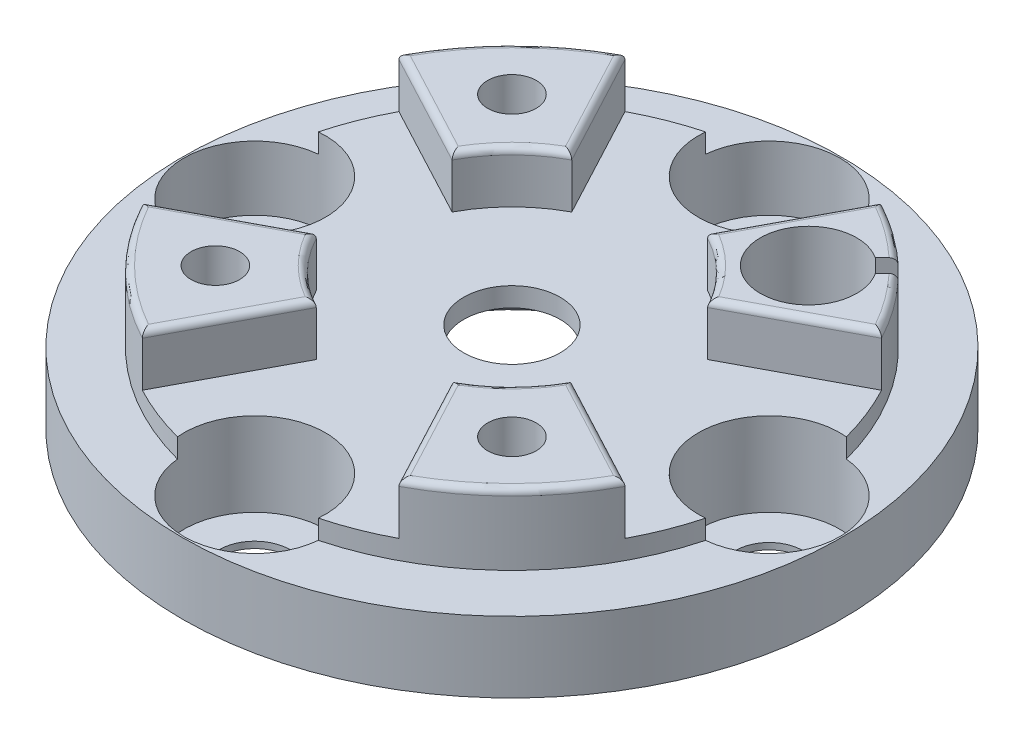
SolidWorks part; units mm, degrees
ref_plane "Front Plane" through (0, 0, 0) normal (0, 0, 1) x (1, 0, 0)
ref_plane "Top Plane" through (0, 0, 0) normal (0, 1, 0) x (1, 0, 0)
ref_plane "Right Plane" through (0, 0, 0) normal (1, 0, 0) x (0, 0, -1)
sketch "Sketch2" plane through (0, 0, 0) normal (0, 1, 0) x (1, 0, 0)
  circle A0 centre (0, 0) radius 10.25
  circle A1 centre (8, 0) radius 1.05
  circle A2 centre (0, 8) radius 1.1
  circle A3 centre (-8, 0) radius 1.05
  circle A4 centre (0, -8) radius 1.1
  dimension "D1" = 20.5
  dimension "D6" = 2.1
  dimension "D7" = 2.1
  dimension "D8" = 2.2
  dimension "D9" = 2.2
  dimension "D2" = 8
  dimension "D3" = 16
  dimension "D4" = 8
  dimension "D5" = 16
extrude "Boss-Extrude1" add sketch "Sketch2" along normal blind 2.2
sketch "Sketch3" plane through (0, 2.2, 0) normal (0, 1, 0) x (1, 0, 0)
  circle A0 centre (0, 8) radius 2.2
  circle A1 centre (-8, 0) radius 2.2
  circle A2 centre (0, -8) radius 2.2
  circle A3 centre (8, 0) radius 2.2
extrude "Cut-Extrude1" cut sketch "Sketch3" against normal blind 2
sketch "Sketch4" plane through (0, 2.2, 0) normal (0, 1, 0) x (1, 0, 0)
  circle A0 centre (0, 0) radius 4.125
  dimension "D1" = 8.25
extrude "Cut-Extrude2" cut sketch "Sketch4" against normal through all
sketch "Sketch7" plane through (0, 2.2, 0) normal (0, 1, 0) x (1, 0, 0)
  arc A0 (2.1897, -8.2131) -> (8.2131, -2.1897) centre (0, 0) ccw
  arc A1 (-8.2131, -2.1897) -> (-8.2131, 2.1897) centre (-8, 0) ccw
  arc A3 (-2.1897, 8.2131) -> (2.1897, 8.2131) centre (0, 8) ccw
  arc A4 (2.1897, -8.2131) -> (-2.1897, -8.2131) centre (0, -8) ccw
  arc A5 (-8.2131, -2.1897) -> (-2.1897, -8.2131) centre (0, 0) ccw
  arc A6 (-2.1897, 8.2131) -> (-8.2131, 2.1897) centre (0, 0) ccw
  arc A7 (8.2131, 2.1897) -> (2.1897, 8.2131) centre (0, 0) ccw
  arc A8 (8.2131, 2.1897) -> (8.2131, -2.1897) centre (8, 0) ccw
  dimension "D1" = 17
extrude "Boss-Extrude3" add sketch "Sketch7" along normal blind 0.6
sketch "Sketch8" plane through (0, 2.8, 0) normal (0, 1, 0) x (1, 0, 0)
  circle A0 centre (0, 0) radius 1.5
  dimension "D1" = 3
extrude "Cut-Extrude7" cut sketch "Sketch8" against normal blind 0.6
chamfer "Chamfer2" distance 0.5 angle 40 1 edges at (0, 0, 4.125) first distance on face at (0, 0, 4.125)
sketch "Sketch10" plane through (0, 0, 0) normal (0, -1, 0) x (-1, 0, 0)
  line L0 (0, 8.5) -> (0, 0) construction
  line L1 (0, 0) -> (-8.5, 0) construction
  line L2 (-6.0104, 6.0104) -> (-3.2135, 3.2135) construction
  arc A0 (0, 8.5) -> (-8.5, 0) centre (0, 0) ccw construction
  circle A1 centre (0, 0) radius 4.5445 construction
  circle A2 centre (-4.6119, 4.6119) radius 0.76
  dimension "D1" = 1.52
extrude "Cut-Extrude8" cut sketch "Sketch10" against normal through all
sketch "Sketch11" plane through (0, 2.8, 0) normal (0, 1, 0) x (1, 0, 0)
  circle A0 centre (4.6119, 4.6119) radius 1.5
extrude "Cut-Extrude9" cut sketch "Sketch11" against normal blind 1
sketch "Sketch12" plane through (0, 2.8, 0) normal (0, 1, 0) x (1, 0, 0)
  line L0 (0, 0) -> (4.6119, 4.6119) construction
  line L1 (4.6119, 4.6119) -> (7.2478, 7.2478)
  circle A0 centre (0, 0) radius 10.25 construction
extrude "Cut-Extrude-Thin1" cut sketch "Sketch12" against normal blind 0.6 and the other way through all thin thin type mid plane wall 0.6
sketch "Sketch13" plane through (0, 2.8, 0) normal (0, 1, 0) x (1, 0, 0)
  line L0 (4.6119, 4.6119) -> (0, 0) construction
  line L1 (0, 0) -> (-4.6119, -4.6119) construction
  circle A0 centre (-4.6119, -4.6119) radius 0.755
  dimension "D1" = 1.51
extrude "Cut-Extrude10" cut sketch "Sketch13" against normal through all both and the other way through all
sketch "Sketch14" plane through (0, 2.8, 0) normal (0, 1, 0) x (1, 0, 0)
  line L0 (0, 0) -> (-4.6119, -4.6119) construction
  line L1 (-4.6119, -4.6119) -> (-4.6119, 4.6119) construction
  line L2 (0, 0) -> (4.6119, 4.6119) construction
  line L3 (4.6119, 4.6119) -> (4.6119, -4.6119) construction
  line L4 (4.6119, 4.6119) -> (-4.6119, 4.6119) construction
  line L5 (-4.6119, -4.6119) -> (4.6119, -4.6119) construction
  circle A0 centre (4.6119, -4.6119) radius 0.755
  circle A1 centre (-4.6119, 4.6119) radius 0.755
  circle A2 centre (-4.6119, -4.6119) radius 0.755 construction
extrude "Cut-Extrude11" cut sketch "Sketch14" against normal blind 10
sketch "Sketch16" plane through (0, 2.8, 0) normal (0, 1, 0) x (1, 0, 0)
  line L0 (0, 0) -> (6.0104, -6.0104) construction
  line L1 (0, 0) -> (-6.0104, -6.0104) construction
  line L2 (0, 0) -> (-6.0104, 6.0104) construction
  line L3 (0, 0) -> (6.0104, 6.0104) construction
  line L4 (0, 0) -> (-7.5051, -3.9905) construction
  line L5 (0, 0) -> (-3.9905, -7.5051) construction
  line L6 (0, 0) -> (7.5051, 3.9905) construction
  line L7 (0, 0) -> (3.9905, 7.5051) construction
  line L8 (0, 0) -> (-7.5051, 3.9905) construction
  line L9 (0, 0) -> (-3.9905, 7.5051) construction
  line L10 (0, 0) -> (7.5051, -3.9905) construction
  line L11 (0, 0) -> (3.9905, -7.5051) construction
  line L12 (-2.7076, -5.0922) -> (-3.9905, -7.5051)
  line L13 (-5.0922, -2.7076) -> (-7.5051, -3.9905)
  line L14 (-5.0922, 2.7076) -> (-7.5051, 3.9905)
  line L15 (-2.7076, 5.0922) -> (-3.9905, 7.5051)
  line L16 (2.7076, 5.0922) -> (3.9905, 7.5051)
  line L17 (5.0922, 2.7076) -> (7.5051, 3.9905)
  line L18 (5.0922, -2.7076) -> (7.5051, -3.9905)
  line L19 (2.7076, -5.0922) -> (3.9905, -7.5051)
  line L20 (5.7945, 6.2188) -> (5.439, 5.8633)
  line L21 (6.2188, 5.7945) -> (5.8633, 5.439)
  line L22 (-2.7076, -5.0922) -> (-2.1126, -3.9733)
  line L23 (-5.0922, -2.7076) -> (-3.9733, -2.1126)
  line L24 (-5.0922, 2.7076) -> (-3.9733, 2.1126)
  line L25 (-2.7076, 5.0922) -> (-2.1126, 3.9733)
  line L26 (2.7076, 5.0922) -> (2.1126, 3.9733)
  line L27 (5.0922, 2.7076) -> (3.9733, 2.1126)
  line L28 (5.0922, -2.7076) -> (3.9733, -2.1126)
  line L29 (2.7076, -5.0922) -> (2.1126, -3.9733)
  arc A0 (2.1897, -8.2131) -> (8.2131, -2.1897) centre (0, 0) ccw construction
  arc A1 (-8.2131, -2.1897) -> (-2.1897, -8.2131) centre (0, 0) ccw construction
  arc A2 (-2.1897, 8.2131) -> (-8.2131, 2.1897) centre (0, 0) ccw construction
  arc A3 (-8.2131, -2.1897) -> (-2.1897, -8.2131) centre (0, 0) ccw construction
  arc A4 (8.2131, 2.1897) -> (6.2188, 5.7945) centre (0, 0) ccw construction
  arc A5 (5.7945, 6.2188) -> (2.1897, 8.2131) centre (0, 0) ccw construction
  arc A6 (-2.1897, 8.2131) -> (-8.2131, 2.1897) centre (0, 0) ccw construction
  arc A7 (2.1897, -8.2131) -> (8.2131, -2.1897) centre (0, 0) ccw construction
  arc A9 (3.9905, -7.5051) -> (7.5051, -3.9905) centre (0, 0) ccw
  arc A11 (-7.5051, -3.9905) -> (-3.9905, -7.5051) centre (0, 0) ccw
  arc A12 (-3.9905, 7.5051) -> (-7.5051, 3.9905) centre (0, 0) ccw
  arc A14 (7.5051, 3.9905) -> (6.2188, 5.7945) centre (0, 0) ccw
  circle A16 centre (-4.6119, -4.6119) radius 0.755
  circle A17 centre (-4.6119, 4.6119) radius 0.755
  circle A19 centre (4.6119, -4.6119) radius 0.755
  arc A22 (5.7945, 6.2188) -> (3.9905, 7.5051) centre (0, 0) ccw
  arc A23 (3.9733, 2.1126) -> (2.1126, 3.9733) centre (0, 0) ccw
  circle A24 centre (4.6119, 4.6119) radius 1.5
  arc A25 (-2.1126, 3.9733) -> (-3.9733, 2.1126) centre (0, 0) ccw
  arc A26 (-3.9733, -2.1126) -> (-2.1126, -3.9733) centre (0, 0) ccw
  arc A27 (2.1126, -3.9733) -> (3.9733, -2.1126) centre (0, 0) ccw
  circle M12 centre (4.6119, -4.6119) radius 0.755
  circle M13 centre (-4.6119, 4.6119) radius 0.755
  circle M14 centre (-4.6119, -4.6119) radius 0.755
  arc M16 (8.2131, 2.1897) -> (6.2188, 5.7945) centre (0, 0) ccw
  line M17 (6.2188, 5.7945) -> (5.8633, 5.439)
  arc M18 (5.8633, 5.439) -> (5.439, 5.8633) centre (4.6119, 4.6119) cw
  line M19 (5.439, 5.8633) -> (5.7945, 6.2188)
  arc M20 (5.7945, 6.2188) -> (2.1897, 8.2131) centre (0, 0) ccw
  arc M22 (-2.1897, 8.2131) -> (-8.2131, 2.1897) centre (0, 0) ccw
  arc M24 (-8.2131, -2.1897) -> (-2.1897, -8.2131) centre (0, 0) ccw
  arc M26 (2.1897, -8.2131) -> (8.2131, -2.1897) centre (0, 0) ccw
  dimension "D5" = 9
  dimension "D1" = 17
  dimension "D2" = 17
  dimension "D3" = 17
  dimension "D4" = 17
extrude "Boss-Extrude5" add sketch "Sketch16" along normal blind 1.6 contours A26 L23 L13 L12 L22 M24 M14 | A25 L25 L15 L14 L24 M22 M13 | A23 L27 L17 L16 L26 M16 M17 M18 M19 M20 | A27 L29 L19 L18 L28 M26 M12 region at (-3.4164, 2.8, 6.2628) region at (-6.2628, 2.8, -3.4164) region at (3.4164, 2.8, -6.2628) region at (6.2628, 2.8, 3.4164)
fillet "Fillet1" radius 0.2 17 edges at (6.0104, 4.4, 6.0104) (3.0516, 4.4, 5.7392) (3.182, 4.4, 3.182) (5.7392, 4.4, 3.0516) (3.0516, 4.4, -5.7392) (4.9346, 4.4, -6.921) (6.921, 4.4, -4.9346) (5.7392, 4.4, -3.0516) (3.182, 4.4, -3.182) (-6.0104, 4.4, -6.0104) (-3.0516, 4.4, -5.7392) (-3.182, 4.4, -3.182) (-5.7392, 4.4, -3.0516) (-5.7392, 4.4, 3.0516) (-3.182, 4.4, 3.182) (-3.0516, 4.4, 5.7392) (-6.0104, 4.4, 6.0104)
